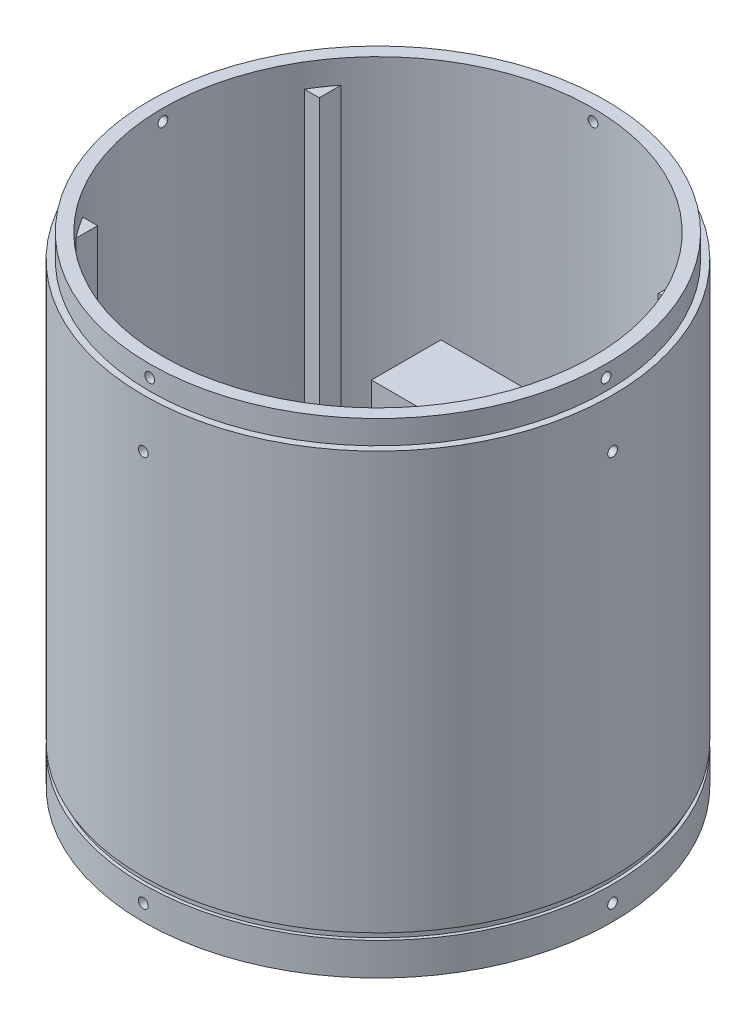
SolidWorks part; units mm, degrees
ref_plane "前基準面" through (0, 0, 0) normal (0, 0, 1) x (1, 0, 0)
ref_plane "上基準面" through (0, 0, 0) normal (0, 1, 0) x (1, 0, 0)
ref_plane "右基準面" through (0, 0, 0) normal (1, 0, 0) x (0, 0, -1)
sketch "草圖6" plane through (0, 0, 0) normal (0, 1, 0) x (1, 0, 0)
  line L0 (0, 0) -> (-95.9878, 0) construction
  line L1 (0, 0) -> (-70, 0) construction
  circle A0 centre (0, 0) radius 66
  circle A1 centre (0, 0) radius 70
  circle A2 centre (0, 0) radius 72
  point P5 (-70, 0)
  point P10 (0, 70)
  point P11 (70, 0)
  point P12 (0, -70)
  dimension "D1" = 2
  dimension "D2" = 4
  dimension "D3" = 144
  dimension "D4" = 4
  dimension "D5" = 70
sketch "草圖7" plane through (0, 0, 0) normal (0, 1, 0) x (1, 0, 0)
  line L1 (-34, 34) -> (34, 34)
  line L2 (-34, 34) -> (-34, -34)
  line L3 (-34, -34) -> (34, -34)
  line L4 (34, 34) -> (34, -34)
  line L5 (-34, 34) -> (34, -34) construction
  line L6 (-34, -34) -> (34, 34) construction
  point P0 (0, 0)
  point P7 (-30, 30)
  point P10 (30, 30)
  point P11 (30, -30)
  point P12 (-30, -30)
  point P13 (0, 0)
  dimension "D1" = 68
  dimension "D2" = 4
  dimension "D3" = 4
extrude "填料-伸長1" add sketch "草圖6" along normal blind 140 contours A2 A1 region at (-71.7964, 0, 0)
extrude "填料-伸長2" add sketch "草圖6<15>" along normal blind 147.25 contours A1 A0 region at (-68.0201, 0, 0)
sketch "草圖6<15>" plane through (0, 0, 0) normal (0, 1, 0) x (1, 0, 0) same geometry as "草圖6"
extrude "填料-伸長3" add sketch "草圖6<16>" along normal blind 3 contours A0 region at (0, 0, 0)
sketch "草圖6<16>" plane through (0, 0, 0) normal (0, 1, 0) x (1, 0, 0) same geometry as "草圖6"
sketch "草圖9" plane through (0, 0, 0) normal (0, 1, 0) x (1, 0, 0)
  line L0 (0, 0) -> (0, 39.247) construction
  line L1 (52, 67.0867) -> (52, -71.5265)
  line L2 (-96.5637, -34) -> (97.4044, -34)
  line L4 (-52, 67.0867) -> (-52, -71.5265)
  line L5 (-56.5685, 34) -> (88.304, 34)
  circle A0 centre (0, 0) radius 66
  circle A1 centre (0, 0) radius 70
  circle A2 centre (0, 0) radius 72
  dimension "D1" = 2
  dimension "D2" = 4
  dimension "D3" = 144
  dimension "D4" = 52
extrude "填料-伸長6" add sketch "草圖9" along normal up to surface (140 mm away) contours L4 A0 L5 | L2 A0 L4 | L1 A0 L2 | L5 A0 L1 region at (53.5564, 0, -36.2624) region at (-53.5564, 0, -36.2624) region at (53.5564, 0, 36.2624) region at (-53.5564, 0, 36.2624) up to face at (0, 140, 70)
sketch "草圖30" plane through (0, 0, 0) normal (1, 0, 0) x (0, 0, -1)
  line L0 (0, 147.25) -> (0, 140) construction
  line L1 (70, 147.25) -> (-70, 147.25) construction
  line L2 (72, 140) -> (-72, 140) construction
  point P6 (0, 143.625)
  dimension "D1" = 3.625
hole_wizard "Ø2.5mm 定位孔3" positions "3D草圖17" profile "草圖31" hole size "Ø3.0" standard "JIS" end condition up to next
sketch3d "3D草圖17"
  point P0 (70, 143.625, 0)
sketch "草圖31" plane through (70, 143.625, 0) normal (0, 1, 0) x (0, 0, -1)
  line L0 (0, 0) -> (0, 136.001)
  line L1 (0, 136.001) -> (1.5, 136.001)
  line L2 (1.5, 136.001) -> (1.5, 0)
  line L5 (1.5, 0) -> (0, 0)
  line L11 (0, -6.35) -> (0, 107.95) construction
  dimension "貫穿孔直徑" = 3
  dimension "貫穿孔深度" = 136.001
pattern_circular "環狀複製排列1" count 4 over 360 about axis through (0, 147.25, 0) along (0, 1, 0) of "Ø2.5mm 定位孔3"
ref_plane "平面4" through (0, 0, 0) normal (0, 0, 1) x (1, 0, 0)
sketch "草圖33" plane through (0, 0, 0) normal (0, 0, 1) x (1, 0, 0)
  line L5 (-72, 12) -> (-71, 12)
  line L6 (-71, 12) -> (-71, 10)
  line L7 (-71, 10) -> (-72, 10)
  line L9 (72, 0) -> (-72, 0) construction
  line L10 (-72, 12) -> (-72, 10)
  line L11 (-72, 140) -> (-72, 0) construction
  dimension "D1" = 1
  dimension "D2" = 2
  dimension "D6" = 10
revolve "除料-旋轉1" cut sketch "草圖33" angle 360 about L0
sketch "草圖35" plane through (0, 0, 0) normal (0, 0, 1) x (1, 0, 0)
  line L0 (-72, 10) -> (-72, 0) construction
  point P0 (-72, 5)
hole_wizard "Ø3.0mm 定位孔1" positions "3D草圖20" profile "草圖37" hole size "Ø3.0" standard "JIS"
sketch3d "3D草圖20"
  point P0 (-72, 5, 0)
sketch "草圖37" plane through (-72, 5, 0) normal (0, 1, 0) x (0, 0, 1)
  line L0 (0, 0) -> (0, 4.9013)
  line L1 (0, 4.9013) -> (1.5, 4)
  line L2 (1.5, 4) -> (1.5, 0)
  line L5 (1.5, 0) -> (0, 0)
  line L10 (0, 4.9013) -> (-1.5, 4) construction
  line L11 (0, -6.35) -> (0, 107.95) construction
  dimension "鑽孔直徑" = 3
  dimension "鑽孔深度" = 4
  dimension "導頭角度" = 118
pattern_circular "環狀複製排列2" count 4 over 360 about axis through (0, 147.25, 0) along (0, -1, 0) of "Ø3.0mm 定位孔1"
sketch "草圖39" plane through (0, 0, 0) normal (0, 1, 0) x (1, 0, 0)
  line L0 (-56.5685, 34) -> (56.5685, 34)
  line L2 (-56.5685, -34) -> (56.5685, -34)
  line L5 (0, 0) -> (0, 19.0172) construction
  line L6 (0, 0) -> (-12.2861, 0) construction
  line L7 (-56.707, 13) -> (-56.707, -13)
  line L8 (-64.707, 13) -> (64.707, 13)
  line L9 (56.707, 13) -> (56.707, -13)
  line L10 (-64.707, -13) -> (64.7924, -12.5675)
  arc A0 (-64.707, -13) -> (-56.5685, -34) centre (0, 0) ccw
  arc A3 (-56.5685, 34) -> (-64.707, 13) centre (0, 0) ccw
  arc A4 (64.707, 13) -> (56.5685, 34) centre (0, 0) ccw
  arc A5 (56.5685, -34) -> (64.7924, -12.5675) centre (0, 0) ccw
  point P12 (-49, 22)
  point P24 (56.707, 0)
  point P27 (-56.707, 0)
  dimension "D1" = 8
  dimension "D2" = 13
  dimension "D5" = 12
sketch "草圖40" plane through (0, 3, 0) normal (0, 1, 0) x (1, 0, 0)
  line L0 (-34, 34) -> (34, 34) construction
  line L1 (-36, 55.3173) -> (36, 55.3173)
  line L2 (-36, 55.3173) -> (-36, 34)
  line L3 (-36, 34) -> (36, 34)
  line L4 (36, 55.3173) -> (36, 34)
  line L5 (-36, 55.3173) -> (36, 34) construction
  line L6 (-36, 34) -> (36, 55.3173) construction
  circle A1 centre (0, 0) radius 66 construction
  point P0 (0, 44.6586)
  dimension "D1" = 21.3173
  dimension "D2" = 72
sketch "草圖41" plane through (0, 3, 0) normal (0, 1, 0) x (1, 0, 0)
  line L0 (0, 0) -> (-95.9878, 0) construction
  line L1 (-63.7154, 5.5) -> (56.2846, 5.5)
  line L2 (-63.7154, 5.5) -> (-63.7154, -5.5)
  line L3 (-63.7154, -5.5) -> (56.2846, -5.5)
  line L4 (56.2846, 5.5) -> (56.2846, -5.5)
  line L5 (-63.7154, 5.5) -> (56.2846, -5.5) construction
  line L6 (-63.7154, -5.5) -> (56.2846, 5.5) construction
  point P0 (-3.7154, 0)
  dimension "D1" = 11
  dimension "D2" = 120
extrude "填料-伸長8" add sketch "草圖40" along normal blind 70 separate body
pattern_linear "直線複製排列2" count 2 spacing 120 along (0, 1, 0) of "環狀複製排列2"
